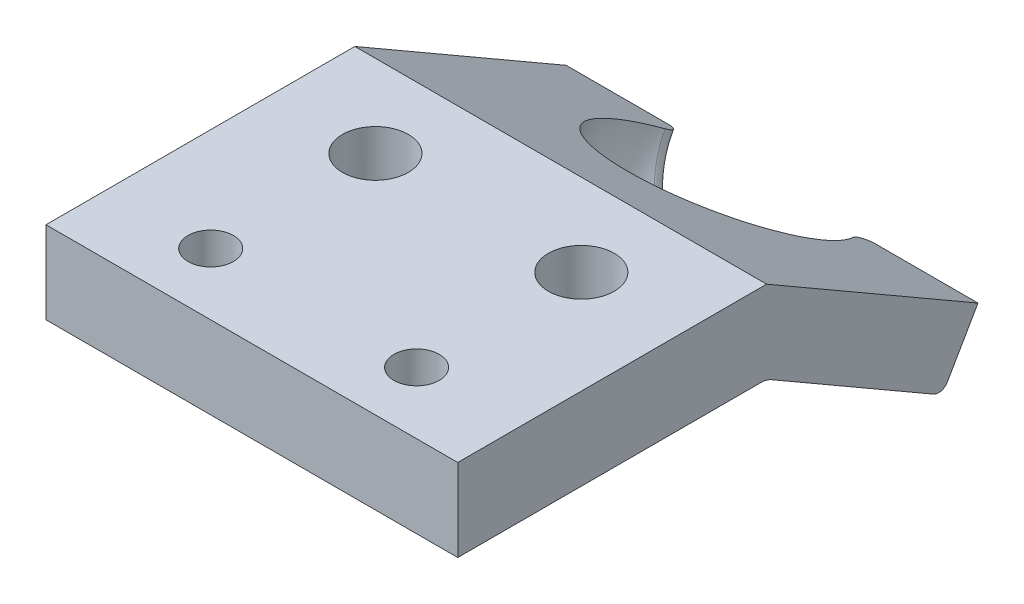
SolidWorks part; units mm, degrees
ref_plane "前视基准面" through (0, 0, 0) normal (0, 0, 1) x (1, 0, 0)
ref_plane "上视基准面" through (0, 0, 0) normal (0, 1, 0) x (1, 0, 0)
ref_plane "右视基准面" through (0, 0, 0) normal (1, 0, 0) x (0, 0, -1)
sketch "草图1" plane through (0, 0, 0) normal (0, 1, 0) x (1, 0, 0)
  line L0 (0, 40) -> (0, -40) construction
  line L1 (46.188, 0) -> (23.094, 40) construction
  line L2 (23.094, 40) -> (-23.094, 40) construction
  line L3 (-23.094, 40) -> (-46.188, 0) construction
  line L4 (-46.188, 0) -> (-23.094, -40) construction
  line L5 (-23.094, -40) -> (23.094, -40) construction
  line L6 (23.094, -40) -> (46.188, 0) construction
  line L7 (11.547, 40) -> (-11.547, 40)
  line L8 (-11.547, 40) -> (-40.4145, -10)
  line L9 (-40.4145, -10) -> (-28.8675, -30)
  line L10 (-28.8675, -30) -> (28.8675, -30)
  line L11 (40.4145, -10) -> (28.8675, -30)
  line L12 (11.547, 40) -> (40.4145, -10)
  circle A0 centre (0, 0) radius 40 construction
  circle A1 centre (0, 0) radius 5
  point P16 (0, -30)
  dimension "D1" = 80
  dimension "D4" = 10
  dimension "D2" = 10
  dimension "D3" = 10
extrude "凸台-拉伸1" add sketch "草图1" along normal blind 8
sketch "草图2" plane through (0, 0, 0) normal (1, 0, 0) x (0, 0, -1)
  line L0 (40, 8) -> (40, 0)
  line L2 (40, 0) -> (48.5359, -4.9282)
  line L3 (40, 8) -> (52, 1.0718)
  line L5 (52, 1.0718) -> (48.5359, -4.9282)
  dimension "D1" = 60
  dimension "D2" = 12
extrude "凸台-拉伸2" add sketch "草图2" along normal blind 10 and the other way blind 10
sketch "草图4" plane through (0, 0, 0) normal (1, 0, 0) x (0, 0, -1)
  line L0 (49.4019, 2.5718) -> (45.9378, -3.4282) construction
  line L1 (52, 1.0718) -> (40, 8) construction
  line L2 (40, 0) -> (48.5359, -4.9282) construction
  line L3 (48.5359, -4.9282) -> (52, 1.0718) construction
  line L4 (50.2199, 3.9885) -> (45.1199, -4.8449)
  arc A0 (50.2199, 3.9885) -> (45.1199, -4.8449) centre (47.6699, -0.4282) cw
  dimension "D2" = 5.1
  dimension "D1" = 3
revolve "切除-旋转1" cut sketch "草图4" angle 360 about L0
fillet "圆角1" radius 0.5 8 edges at (6.1192, -4.9282, -48.5359) (-6.1192, -4.9282, -48.5359) (-6.1192, 1.0718, -52) (-4.1243, -1.9282, -50.2679) (0, -1.5567, -42.6963) (4.1243, -1.9282, -50.2679) (0, 4.4433, -46.1604) (6.1192, 1.0718, -52)
sketch "草图5" plane through (0, 0, 0) normal (1, 0, 0) x (0, 0, -1)
  line L0 (50.2679, -1.9282) -> (40, 4) construction
  line L1 (48.7859, -4.4952) -> (51.75, 0.6388) construction
  line L2 (40, 8) -> (40, 0) construction
  line L3 (40, 4) -> (25, 4) construction
  dimension "D1" = 15
sketch "草图6" plane through (0, 8, 0) normal (0, 1, 0) x (1, 0, 0)
  line L0 (0, 32.5) -> (-10, 32.5) construction
  line L1 (0, 40) -> (0, 25) construction
  line L2 (0, 32.5) -> (10, 32.5) construction
  line L3 (0, 40) -> (0, 25) construction
  line L4 (0, 50.2679) -> (0, 40) construction
  line L5 (-5, 36) -> (-5, 28) construction
  circle A0 centre (-5, 36) radius 1.6
  circle A1 centre (5, 36) radius 1.6
  circle A2 centre (-5, 28) radius 1.1
  circle A3 centre (5, 28) radius 1.1
  circle A4 centre (-5, 36) radius 3 construction
  circle A5 centre (-5, 28) radius 2 construction
  dimension "D1" = 3.5
  dimension "D2" = 5
  dimension "D3" = 3.2
  dimension "D5" = 2.2
  dimension "D6" = 6
  dimension "D7" = 4
  dimension "D4" = 8
extrude "切除-拉伸1" cut sketch "草图6" against normal through all
sketch "草图7" plane through (0, 0, 0) normal (1, 0, 0) x (0, 0, -1)
  line L0 (50.2679, -1.9282) -> (40, 4) construction
  line L1 (40, 4) -> (25, 4) construction
  line L2 (50.2679, -1.9282) -> (40, 4)
  line L3 (40, 4) -> (25, 4)
  line L4 (25, 4) -> (25, 0)
  line L5 (-10, 0) -> (40, 0) construction
  line L11 (50.2679, -1.9282) -> (51.75, 0.6388)
  line L12 (51.75, 0.6388) -> (52, 1.0718)
  line L13 (52, 1.0718) -> (51.567, 1.3218)
  line L14 (51.567, 1.3218) -> (40, 8) construction
  line L15 (51.567, 1.3218) -> (40, 8)
  line L16 (40, 8) -> (-30, 8)
  line L17 (-30, 8) -> (-30, 0)
  line L18 (-30, 0) -> (25, 0)
extrude "切除-拉伸2" cut sketch "草图7" against normal through all and the other way through all
sketch "草图8" plane through (0, 4, 0) normal (0, 1, 0) x (1, 0, 0)
  line L0 (-10, 40) -> (-10, 25) construction
  line L1 (-20.2073, 25) -> (20.2073, 25) construction
  line L2 (10, 40) -> (10, 25) construction
  line L3 (-10, 40) -> (-11.547, 40)
  line L4 (-11.547, 40) -> (-20.2073, 25)
  line L5 (-20.2073, 25) -> (-10, 25)
  line L6 (-10, 25) -> (-10, 40)
  line L7 (10, 40) -> (11.547, 40)
  line L8 (11.547, 40) -> (20.2073, 25)
  line L9 (20.2073, 25) -> (10, 25)
  line L10 (10, 25) -> (10, 40)
extrude "切除-拉伸3" cut sketch "草图8" against normal through all
fillet "圆角2" radius 1 1 edges at (0, 0, -40)
